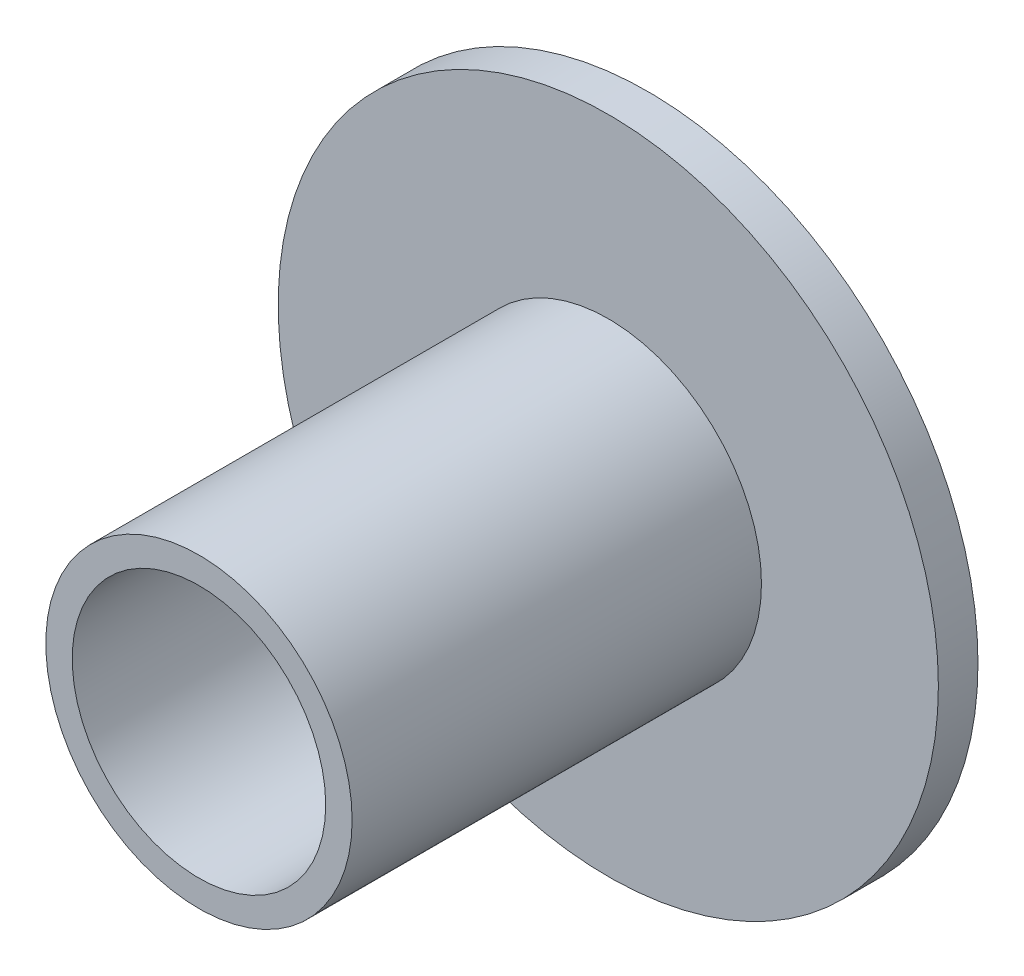
SolidWorks part; units mm, degrees
ref_plane "Front Plane" through (0, 0, 0) normal (0, 0, 1) x (1, 0, 0)
ref_plane "Top Plane" through (0, 0, 0) normal (0, 1, 0) x (1, 0, 0)
ref_plane "Right Plane" through (0, 0, 0) normal (1, 0, 0) x (0, 0, -1)
sketch "Sketch1" plane through (0, 0, 0) normal (0, 0, 1) x (1, 0, 0)
  circle A0 centre (0, 0) radius 1.2192
  circle A1 centre (0, 0) radius 1.4732
  circle A2 centre (0, 0) radius 3.175
  dimension "D1" = 2.4384
  dimension "D2" = 2.9464
  dimension "D3" = 6.35
extrude "Boss-Extrude1" add sketch "Sketch1" against normal blind 0.381 contours A1 A0 | A2 A1 region at (-1.4315, 0, 0) region at (-3.0852, 0, 0)
extrude "Boss-Extrude2" add sketch "Sketch1<3>" along normal blind 3.937 contours A1 A0 region at (-1.4315, 0, 0)
sketch "Sketch1<3>" plane through (0, 0, 0) normal (0, 0, 1) x (1, 0, 0) same geometry as "Sketch1"
